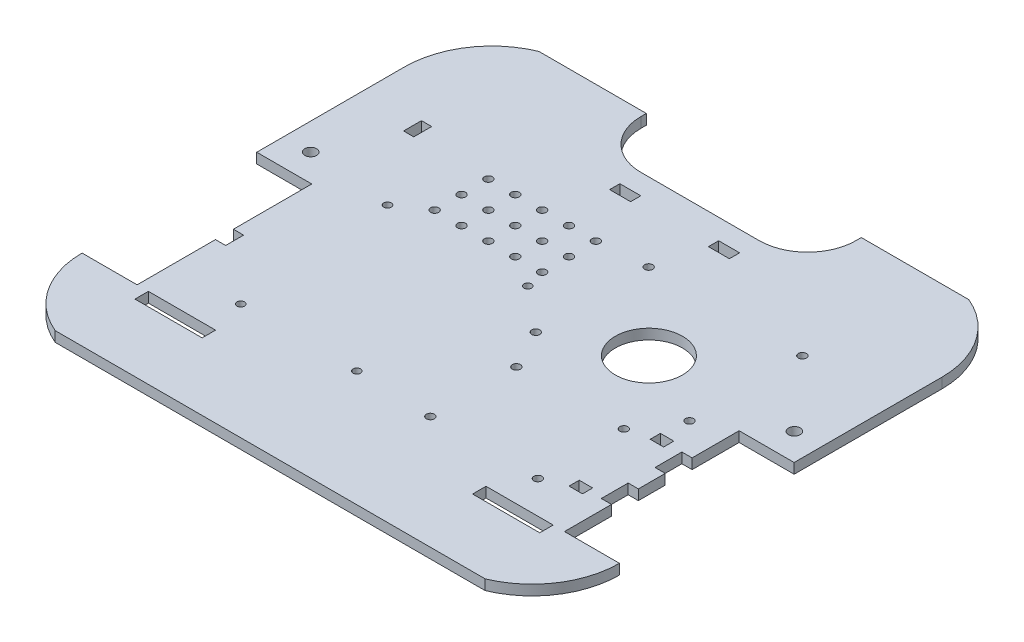
SolidWorks part; units mm, degrees
ref_plane "Front Plane" through (0, 0, 0) normal (0, 0, 1) x (1, 0, 0)
ref_plane "Top Plane" through (0, 0, 0) normal (0, 1, 0) x (1, 0, 0)
ref_plane "Right Plane" through (0, 0, 0) normal (1, 0, 0) x (0, 0, -1)
sketch "Sketch1" plane through (0, 0, 0) normal (0, 1, 0) x (1, 0, 0)
  line L1 (-127, 114.3) -> (127, 114.3)
  line L2 (-127, 114.3) -> (-127, -114.3)
  line L3 (-127, -114.3) -> (127, -114.3)
  line L4 (127, 114.3) -> (127, -114.3)
  line L5 (-127, 114.3) -> (127, -114.3) construction
  line L6 (-127, -114.3) -> (127, 114.3) construction
  point P0 (0, 0)
  dimension "D1" = 254
  dimension "D2" = 228.6
extrude "Boss-Extrude1" add sketch "Sketch1" along normal blind 4.826
sketch "Sketch2" plane through (0, 4.826, 0) normal (0, 1, 0) x (1, 0, 0)
  line L0 (-127, 114.3) -> (-127, -114.3) construction
  line L1 (-127, 6.35) -> (-101, 6.35)
  line L2 (-127, 6.35) -> (-127, -76.2)
  line L3 (-127, -76.2) -> (-101, -76.2)
  line L4 (-101, 6.35) -> (-101, -76.2)
  line L5 (127, -114.3) -> (127, 114.3) construction
  line L6 (127, 6.35) -> (101, 6.35)
  line L7 (127, 6.35) -> (127, -76.2)
  line L8 (127, -76.2) -> (101, -76.2)
  line L9 (101, 6.35) -> (101, -76.2)
  line L10 (-127, -114.3) -> (127, -114.3) construction
  dimension "D1" = 38.1
  dimension "D2" = 38.1
  dimension "D3" = 82.55
  dimension "D4" = 82.55
  dimension "D5" = 26
  dimension "D6" = 26
extrude "Cut-Extrude1" cut sketch "Sketch2" against normal blind 4.826
sketch "Sketch4" plane through (0, 4.826, 0) normal (0, 1, 0) x (1, 0, 0)
  line L0 (0, -114.3) -> (0, 114.3) construction
  line L1 (-127, -114.3) -> (127, -114.3) construction
  line L2 (127, 114.3) -> (-127, 114.3) construction
  line L3 (-127, 76.2) -> (-101.6, 76.2) construction
  line L4 (-127, 114.3) -> (-127, 6.35) construction
  line L5 (-101.6, 76.2) -> (-101.6, 114.3) construction
  line L6 (-127, 76.2) -> (-127, 114.3)
  line L7 (-127, 114.3) -> (-101.6, 114.3)
  line L8 (127, 76.2) -> (127, 114.3)
  line L9 (127, 114.3) -> (101.6, 114.3)
  arc A0 (-127, 76.2) -> (-101.6, 114.3) centre (-85.725, 76.2) cw
  arc A1 (127, 76.2) -> (101.6, 114.3) centre (85.725, 76.2) ccw
  dimension "D2" = 38.1
extrude "Cut-Extrude3" cut sketch "Sketch4" against normal blind 4.826
sketch "Sketch7" plane through (0, 4.826, 0) normal (0, 1, 0) x (1, 0, 0)
  line L0 (0, -114.3) -> (0, 114.3) construction
  line L1 (-127, -114.3) -> (127, -114.3) construction
  line L2 (101.6, 114.3) -> (-101.6, 114.3) construction
  line L3 (50.8, 88.9) -> (50.8, 114.3)
  line L4 (50.8, 88.9) -> (-50.8, 88.9)
  line L5 (0, 88.9) -> (0, 114.3)
  line L6 (50.8, 114.3) -> (-50.8, 114.3)
  line L7 (-50.8, 88.9) -> (-50.8, 114.3)
  line M6 (101.6, 114.3) -> (-101.6, 114.3)
extrude "Cut-Extrude5" cut sketch "Sketch7" against normal blind 4.826 contours L7 L4 L5 M6 | L5 L4 L3 M6 region at (25.4, 4.826, -101.6) region at (-25.4, 4.826, -101.6)
fillet "Fillet9" radius 22.86 1 edges at (-50.8, 2.413, -88.9) type face fillet first side face at (0, 2.413, -88.9) second side face at (-50.8, 2.413, -101.6)
fillet "Fillet10" radius 22.86 1 edges at (50.8, 2.413, -88.9) type face fillet first side face at (11.43, 2.413, -88.9) second side face at (50.8, 2.413, -101.6)
sketch "Sketch8" plane through (0, 4.826, 0) normal (0, 1, 0) x (1, 0, 0)
  line L0 (-127, -76.2) -> (-101.6, -76.2) construction
  line L1 (-101.6, -76.2) -> (-101.6, -114.3) construction
  line L2 (-127, -114.3) -> (127, -114.3) construction
  line L3 (-127, -76.2) -> (-127, -114.3)
  line L4 (-127, -114.3) -> (-101.6, -114.3)
  line L5 (0, -114.3) -> (0, 88.9) construction
  line L6 (27.94, 88.9) -> (-27.94, 88.9) construction
  line L7 (127, -114.3) -> (101.6, -114.3)
  line L8 (127, -76.2) -> (127, -114.3)
  arc A0 (-127, -76.2) -> (-101.6, -114.3) centre (-85.725, -76.2) ccw
  arc A1 (127, -76.2) -> (101.6, -114.3) centre (85.725, -76.2) cw
extrude "Cut-Extrude6" cut sketch "Sketch8" against normal blind 4.826
sketch "Sketch9" plane through (0, 0, 0) normal (0, -1, 0) x (1, 0, 0)
  line L0 (-58.582, 76.2) -> (-101, 76.2) construction
  line L1 (-95.666, 76.2) -> (-63.916, 76.2)
  line L2 (-95.666, 76.2) -> (-95.666, 82.55)
  line L3 (-95.666, 82.55) -> (-63.916, 82.55)
  line L4 (-63.916, 76.2) -> (-63.916, 82.55)
  line L5 (-101, 76.2) -> (-95.666, 76.2) construction
  line L6 (-63.916, 76.2) -> (-58.582, 76.2) construction
  line L7 (0, 114.3) -> (0, -88.9) construction
  line L8 (-101.6, 114.3) -> (101.6, 114.3) construction
  line L9 (27.94, -88.9) -> (-27.94, -88.9) construction
  line L10 (63.916, 76.2) -> (58.582, 76.2) construction
  line L11 (101, 76.2) -> (95.666, 76.2) construction
  line L12 (63.916, 76.2) -> (63.916, 82.55)
  line L13 (95.666, 82.55) -> (63.916, 82.55)
  line L14 (95.666, 76.2) -> (95.666, 82.55)
  line L15 (95.666, 76.2) -> (63.916, 76.2)
  dimension "D1" = 31.75
  dimension "D2" = 6.35
extrude "Cut-Extrude7" cut sketch "Sketch9" against normal through all
sketch "Sketch11" plane through (0, 4.826, 0) normal (0, 1, 0) x (1, 0, 0)
  line L0 (-18.3929, 74.4508) -> (-28.2989, 74.4508) construction
  line L1 (-28.2989, 79.2768) -> (-28.2989, 74.4508) construction
  line L2 (-18.3929, 79.2768) -> (-28.2989, 79.2768) construction
  line L3 (-18.3929, 79.2768) -> (-18.3929, 74.4508) construction
  line L4 (28.2989, 74.4508) -> (18.3929, 74.4508) construction
  line L5 (18.3929, 79.2768) -> (18.3929, 74.4508) construction
  line L6 (28.2989, 79.2768) -> (18.3929, 79.2768) construction
  line L7 (28.2989, 79.2768) -> (28.2989, 74.4508) construction
  line L8 (-18.3929, 74.4508) -> (-28.2989, 74.4508)
  line L9 (-28.2989, 79.2768) -> (-28.2989, 74.4508)
  line L10 (-18.3929, 79.2768) -> (-28.2989, 79.2768)
  line L11 (-18.3929, 79.2768) -> (-18.3929, 74.4508)
  line L12 (28.2989, 74.4508) -> (18.3929, 74.4508)
  line L13 (18.3929, 79.2768) -> (18.3929, 74.4508)
  line L14 (28.2989, 79.2768) -> (18.3929, 79.2768)
  line L15 (28.2989, 79.2768) -> (28.2989, 74.4508)
extrude "Cut-Extrude8" cut sketch "Sketch11" against normal through all
sketch "Sketch13" plane through (0, 4.826, 0) normal (0, 1, 0) x (1, 0, 0)
  line L1 (-4.1249, -61.8428) -> (-4.1249, 17.9132) construction
  circle A0 centre (-10.4749, 24.7159) radius 1.905
  circle A1 centre (-23.1749, 24.7159) radius 1.905
  circle A2 centre (-35.8749, 24.7159) radius 1.905
  circle A3 centre (-48.5749, 24.7159) radius 1.905
  circle A4 centre (-61.2749, 24.7159) radius 1.905
  circle A5 centre (-23.1749, 37.4159) radius 1.905
  circle A6 centre (-35.8749, 37.4159) radius 1.905
  circle A7 centre (-48.5749, 37.4159) radius 1.905
  circle A8 centre (-61.2749, 37.4159) radius 1.905
  circle A9 centre (-23.1749, 50.1159) radius 1.905
  circle A10 centre (-35.8749, 50.1159) radius 1.905
  circle A11 centre (-48.5749, 50.1159) radius 1.905
  circle A12 centre (-61.2749, 50.1159) radius 1.905
  circle A13 centre (-10.4749, 37.4159) radius 1.905
  circle A14 centre (-10.4749, 50.1159) radius 1.905
  dimension "D1" = 3.81
  dimension "D4" = 6.35
  dimension "D2" = 5
  dimension "D3" = 3
extrude "Cut-Extrude10" cut sketch "Sketch13" against normal through all
sketch "Sketch14" plane through (0, 4.826, 0) normal (0, 1, 0) x (1, 0, 0)
  circle A0 centre (-68.6409, -59.5568) radius 1.778 construction
  circle A1 centre (-13.7769, -59.5568) radius 1.778 construction
  circle A2 centre (-74.4829, 15.6272) radius 1.778 construction
  circle A3 centre (-8.1889, 15.6272) radius 1.778 construction
  circle A4 centre (-68.6409, -59.5568) radius 1.778
  circle A5 centre (-13.7769, -59.5568) radius 1.778
  circle A6 centre (-74.4829, 15.6272) radius 1.778
  circle A7 centre (-8.1889, 15.6272) radius 1.778
extrude "Cut-Extrude11" cut sketch "Sketch14" against normal through all
sketch "Sketch15" plane through (0, 4.826, 0) normal (0, 1, 0) x (1, 0, 0)
  circle A0 centre (22.2183, -60.7955) radius 1.905 construction
  circle A1 centre (22.2183, -20.1555) radius 1.905 construction
  circle A2 centre (73.0183, -60.7955) radius 1.905 construction
  circle A3 centre (73.0183, -20.1555) radius 1.905 construction
  circle A4 centre (22.2183, -60.7955) radius 1.905
  circle A5 centre (22.2183, -20.1555) radius 1.905
  circle A6 centre (73.0183, -60.7955) radius 1.905
  circle A7 centre (73.0183, -20.1555) radius 1.905
extrude "Cut-Extrude12" cut sketch "Sketch15" against normal through all
sketch "Sketch16" plane through (0, 4.826, 0) normal (0, 1, 0) x (1, 0, 0)
  circle A0 centre (85.2532, -1.3646) radius 1.905 construction
  circle A1 centre (12.6092, -1.3646) radius 1.905 construction
  circle A2 centre (12.6092, 51.9754) radius 1.905 construction
  circle A3 centre (85.2532, 51.9754) radius 1.905 construction
  circle A4 centre (85.2532, -1.3646) radius 1.905
  circle A5 centre (12.6092, -1.3646) radius 1.905
  circle A6 centre (12.6092, 51.9754) radius 1.905
  circle A7 centre (85.2532, 51.9754) radius 1.905
extrude "Cut-Extrude13" cut sketch "Sketch16" against normal through all
sketch "Sketch17" plane through (0, 0, 0) normal (0, -1, 0) x (1, 0, 0)
  circle A0 centre (114.3, -19.1646) radius 2.7781 construction
  circle A1 centre (-114.3, -19.1646) radius 2.7781 construction
  circle A2 centre (114.3, -19.1646) radius 2.7781
  circle A3 centre (-114.3, -19.1646) radius 2.7781
extrude "Cut-Extrude14" cut sketch "Sketch17" against normal through all
sketch "Sketch18" plane through (0, 4.826, 0) normal (0, 1, 0) x (1, 0, 0)
  line L0 (101, -53.975) -> (96.174, -53.975) construction
  line L1 (96.174, -41.275) -> (96.174, -53.975) construction
  line L2 (101, -41.275) -> (96.174, -41.275) construction
  line L3 (101, -41.275) -> (101, -53.975) construction
  line L4 (101, -15.875) -> (101, -28.575) construction
  line L5 (101, -15.875) -> (96.174, -15.875) construction
  line L6 (96.174, -15.875) -> (96.174, -28.575) construction
  line L7 (101, -28.575) -> (96.174, -28.575) construction
  line L8 (101, -53.975) -> (96.174, -53.975)
  line L9 (96.174, -41.275) -> (96.174, -53.975)
  line L10 (101, -41.275) -> (96.174, -41.275)
  line L11 (101, -41.275) -> (101, -53.975)
  line L12 (101, -15.875) -> (101, -28.575)
  line L13 (101, -15.875) -> (96.174, -15.875)
  line L14 (96.174, -15.875) -> (96.174, -28.575)
  line L15 (101, -28.575) -> (96.174, -28.575)
extrude "Cut-Extrude15" cut sketch "Sketch18" against normal through all
sketch "Sketch19" plane through (0, 4.826, 0) normal (0, 1, 0) x (1, 0, 0)
  line L0 (-101, -39.1583) -> (-101, -30.6917) construction
  line L1 (-101, -39.1583) -> (-96.174, -39.1583) construction
  line L2 (-96.174, -39.1583) -> (-96.174, -30.6917) construction
  line L3 (-101, -30.6917) -> (-96.174, -30.6917) construction
  line L4 (-101, 49.7417) -> (-101, 58.2083) construction
  line L5 (-101, 49.7417) -> (-96.174, 49.7417) construction
  line L6 (-96.174, 49.7417) -> (-96.174, 58.2083) construction
  line L7 (-101, 58.2083) -> (-96.174, 58.2083) construction
  line L8 (-101, -39.1583) -> (-101, -30.6917)
  line L9 (-101, -39.1583) -> (-96.174, -39.1583)
  line L10 (-96.174, -39.1583) -> (-96.174, -30.6917)
  line L11 (-101, -30.6917) -> (-96.174, -30.6917)
  line L12 (-101, 49.7417) -> (-101, 58.2083)
  line L13 (-101, 49.7417) -> (-96.174, 49.7417)
  line L14 (-96.174, 49.7417) -> (-96.174, 58.2083)
  line L15 (-101, 58.2083) -> (-96.174, 58.2083)
extrude "Cut-Extrude16" cut sketch "Sketch19" against normal through all
sketch "Sketch20" plane through (0, 0, 0) normal (0, -1, 0) x (1, 0, 0)
  line L0 (83.474, 51.689) -> (89.824, 51.689) construction
  line L1 (83.474, 56.515) -> (83.474, 51.689) construction
  line L2 (83.474, 56.515) -> (89.824, 56.515) construction
  line L3 (89.824, 56.515) -> (89.824, 51.689) construction
  line L4 (83.474, 13.335) -> (89.824, 13.335) construction
  line L5 (83.474, 18.161) -> (83.474, 13.335) construction
  line L6 (83.474, 18.161) -> (89.824, 18.161) construction
  line L7 (89.824, 18.161) -> (89.824, 13.335) construction
  line L8 (83.474, 51.689) -> (89.824, 51.689)
  line L9 (83.474, 56.515) -> (83.474, 51.689)
  line L10 (83.474, 56.515) -> (89.824, 56.515)
  line L11 (89.824, 56.515) -> (89.824, 51.689)
  line L12 (83.474, 13.335) -> (89.824, 13.335)
  line L13 (83.474, 18.161) -> (83.474, 13.335)
  line L14 (83.474, 18.161) -> (89.824, 18.161)
  line L15 (89.824, 18.161) -> (89.824, 13.335)
extrude "Cut-Extrude17" cut sketch "Sketch20" against normal blind 4.826
sketch "Sketch21" plane through (0, 0, 0) normal (0, -1, 0) x (1, 0, 0)
  circle A0 centre (48.9312, -15.7789) radius 15.875
  circle A1 centre (85.2532, 1.3646) radius 1.905 construction
  circle A2 centre (12.6092, 1.3646) radius 1.905 construction
  dimension "D1" = 31.75
  dimension "D2" = 36.322
  dimension "D3" = 36.322
extrude "Cut-Extrude18" cut sketch "Sketch21" against normal through all
equation "\"MDF\"= 0.19in"
equation "\"GenDiameter\"= 60mm"
equation "\"GenCutDiameter\" = 1.8in"
equation "\"GenCutDistance\" = 1"
equation "\"TowerHeight\" = 6in"
equation "\"TowerFrontBase\" = 3in"
equation "\"FunnelHeight\" = 1in"
equation "\"FunnelAngle\" = 20"
equation "\"TowerSideBase\" = 3in"
equation "\"BaseLength\" = 9in"
equation "\"BaseWidth\" = 10in"
equation "\"WheelHoleLength\" = 3.25in"
equation "\"WheelHoleWidth\" = 26mm"
equation "\"DropLength\" = 1in"
equation "\"D1@Sketch1\"=\"BaseWidth\""
equation "\"D2@Sketch1\"=\"BaseLength\""
equation "\"D1@Boss-Extrude1\"=\"MDF\""
equation "\"WheelHoleFromBack\" = 1.5in"
equation "\"D1@Sketch2\"=\"WheelHoleFromBack\""
equation "\"D2@Sketch2\"=\"WheelHoleFromBack\""
equation "\"D3@Sketch2\"=\"WheelHoleLength\""
equation "\"D4@Sketch2\"=\"WheelHoleLength\""
equation "\"D5@Sketch2\"=\"WheelHoleWidth\""
equation "\"D6@Sketch2\"=\"WheelHoleWidth\""
equation "\"D1@Cut-Extrude1\"=\"MDF\""
equation "\"DropWidth\" = 8.5in"
equation "\"BumperWidth\" = 1in"
equation "\"D1@Sketch4\"=\"BumperWidth\""
equation "\"D2@Sketch4\"=\"WheelHoleFromBack\""
equation "\"D1@Cut-Extrude3\"=\"MDF\""
equation "\"D1@Sketch7\"=\"DropLength\""
equation "\"D2@Sketch7\"=\"DropWidthTop\"/2"
equation "\"D1@Cut-Extrude5\"=\"MDF\""
equation "\"D1@Sketch8\"=\"BumperWidth\""
equation "\"D1@Cut-Extrude6\"=\"MDF\""
equation "\"DropWidthTop\" = 4in"
equation "\"D1@Cut-Extrude17\"=\"MDF\""
